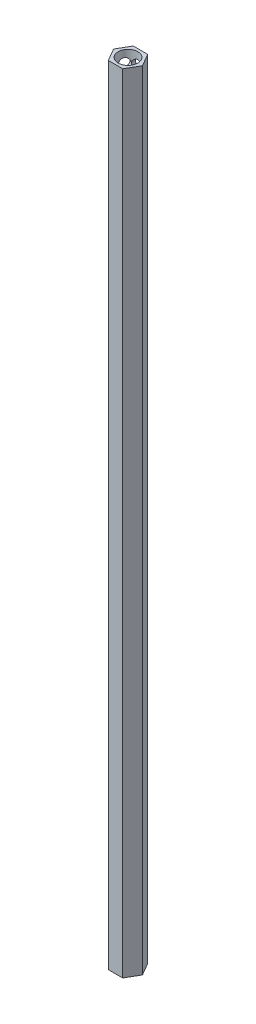
SolidWorks part; units mm, degrees
material "1023 Carbon Steel Sheet (SS)"
ref_plane "Front Plane" through (0, 0, 0) normal (0, 0, 1) x (1, 0, 0)
ref_plane "Top Plane" through (0, 0, 0) normal (0, 1, 0) x (1, 0, 0)
ref_plane "Right Plane" through (0, 0, 0) normal (1, 0, 0) x (0, 0, -1)
sketch "Sketch1" plane through (0, 0, 0) normal (0, 1, 0) x (1, 0, 0)
  line L7 (7.3323, 0) -> (3.6662, 6.35)
  line L8 (3.6662, 6.35) -> (-3.6662, 6.35)
  line L9 (-3.6662, 6.35) -> (-7.3323, 0)
  line L10 (-7.3323, 0) -> (-3.6662, -6.35)
  line L11 (-3.6662, -6.35) -> (3.6662, -6.35)
  line L12 (3.6662, -6.35) -> (7.3323, 0)
  circle A0 centre (0, 0) radius 6.35 construction
  dimension "D1" = 12.7
extrude "Boss-Extrude1" add sketch "Sketch1" along normal mid plane 400
ref_axis "Axis1" through (0, 273.0375, 0) along (0, -1, 0)
hole_wizard "Ø10.0 (10) Diameter Hole1" positions "Sketch4" profile "Sketch2" hole size "Ø10.0" standard "ANSI Metric"
sketch "Sketch4" plane through (0, 200, 0) normal (0, 1, 0) x (1, 0, 0)
  line L0 (-8.0656, 0) -> (8.0656, 0) construction
  line L1 (0, -6.985) -> (0, 6.985) construction
  point P0 (0, 0)
sketch "Sketch2" plane through (0, 200, 0) normal (1, 0, 0) x (0, 0, 1)
  line L0 (0, 0) -> (0, 23.0043)
  line L1 (0, 23.0043) -> (5, 20)
  line L2 (5, 20) -> (5, 0)
  line L5 (5, 0) -> (0, 0)
  line L10 (0, 23.0043) -> (-5, 20) construction
  line L11 (0, -6.35) -> (0, 107.95) construction
  dimension "Hole Dia." = 10
  dimension "Hole Depth" = 20
  dimension "Drill Angle" = 118
hole_wizard "Ø10.0 (10) Diameter Hole2" positions "Sketch6" profile "Sketch5" hole size "Ø10.0" standard "ANSI Metric"
sketch "Sketch6" plane through (0, -200, 0) normal (0, -1, 0) x (-1, 0, 0)
  line L0 (-8.0656, 0) -> (8.0656, 0) construction
  line L1 (0, 6.985) -> (0, -6.985) construction
  point P0 (0, 0)
sketch "Sketch5" plane through (0, -200, 0) normal (1, 0, 0) x (0, 0, -1)
  line L0 (0, 0) -> (0, 23.0043)
  line L1 (0, 23.0043) -> (5, 20)
  line L2 (5, 20) -> (5, 0)
  line L5 (5, 0) -> (0, 0)
  line L10 (0, 23.0043) -> (-5, 20) construction
  line L11 (0, -6.35) -> (0, 107.95) construction
  dimension "Hole Dia." = 10
  dimension "Hole Depth" = 20
  dimension "Drill Angle" = 118
hole_wizard "M6x1.0 Tapped Hole3" positions "Sketch8" profile "Sketch7" tap size "M6x1.0" standard "ANSI Metric" end condition up to next
sketch "Sketch8" plane through (0, 0, -6.35) normal (0, 0, -1) x (-1, 0, 0)
  line L0 (-3.6662, -200) -> (3.6662, -200) construction
  line L1 (-3.6662, 200) -> (3.6662, 200) construction
  point P0 (0, -194)
  point P2 (0, 194)
  dimension "D1" = 6
  dimension "D2" = 6
cosmetic thread "Hole Thread3" parameters "D2"=6
cosmetic thread "Hole Thread4" parameters "D2"=6
sketch "Sketch7" plane through (0, -194, -6.35) normal (1, 0, 0) x (0, 1, 0)
  line L0 (0, 0) -> (0, 1.35)
  line L1 (0, 1.35) -> (2.5, 1.35)
  line L2 (2.5, 1.35) -> (2.5, 0)
  line L5 (2.5, 0) -> (0, 0)
  line L11 (0, -6.35) -> (0, 107.95) construction
  dimension "Thru Tap Drill Dia." = 5
  dimension "Thru Tap Drill Depth" = 1.35
ref_plane "Plane1" through (0, 0, 0) normal (0.5, 0, -0.866) x (0, -1, 0)
hole_wizard "M6x1.0 Tapped Hole4" positions "Sketch12" profile "Sketch11" tap size "M6x1.0" standard "ANSI Metric" end condition up to next
sketch "Sketch12" plane through (-5.4993, 0, -3.175) normal (-0.866, 0, -0.5) x (-0.5, 0, 0.866)
  line L0 (0, 5.041) -> (0, -5.041) construction
  line L1 (-3.6662, 200) -> (3.6662, 200) construction
  line L2 (-3.6662, -200) -> (3.6662, -200) construction
  point P0 (0, 194)
  point P3 (0, -194)
  dimension "D1" = 6
  dimension "D2" = 6
sketch "Sketch11" plane through (-5.4993, 194, -3.175) normal (0, 1, 0) x (-0.5, 0, 0.866)
  line L0 (0, 0) -> (0, 1.35)
  line L1 (0, 1.35) -> (2.5, 1.35)
  line L2 (2.5, 1.35) -> (2.5, 0)
  line L5 (2.5, 0) -> (0, 0)
  line L11 (0, -6.35) -> (0, 107.95) construction
  dimension "Thru Tap Drill Dia." = 5
  dimension "Thru Tap Drill Depth" = 1.35
cosmetic thread "Hole Thread5" parameters "D2"=6
cosmetic thread "Hole Thread6" parameters "D2"=6
